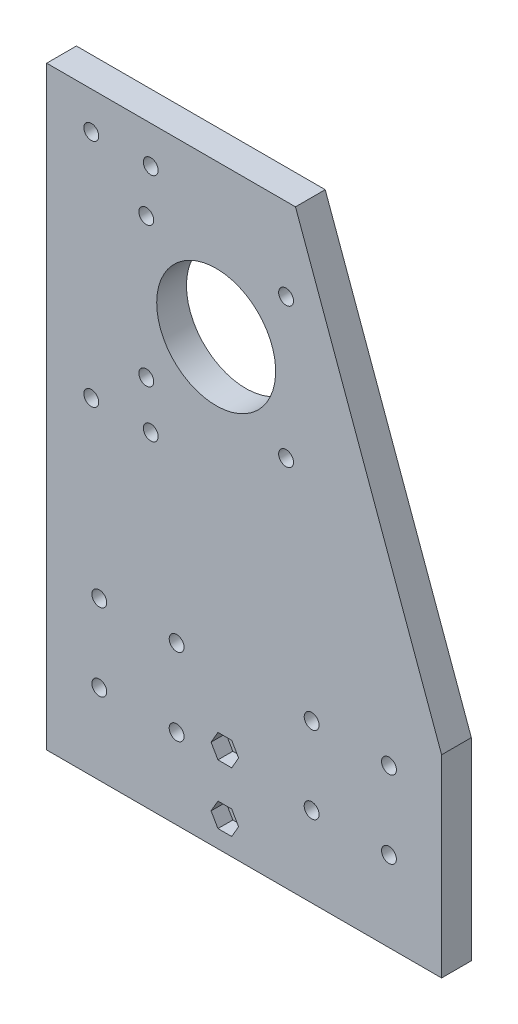
SolidWorks part; units mm, degrees
other "Markup1"
sketch "Sketch3" plane through (0, 200, 35) normal (-0.0073, 0.0178, 0.9998) x (0.9997, -0.0226, 0.0077)
ref_plane "Front Plane" through (0, 0, 0) normal (0, 0, 1) x (1, 0, 0)
ref_plane "Top Plane" through (0, 0, 0) normal (0, 1, 0) x (1, 0, 0)
ref_plane "Right Plane" through (0, 0, 0) normal (1, 0, 0) x (0, 0, -1)
sketch "Sketch1" plane through (0, 0, 0) normal (0, 0, 1) x (1, 0, 0)
  line L0 (66.4, -5.8678) -> (66.4, 56.1407) construction
  line L5 (0, 0) -> (132.8, 0)
  line L6 (0, 0) -> (0, 200)
  line L7 (0, 200) -> (83.664, 200)
  line L8 (132.8, 0) -> (132.8, 65)
  line L9 (71.4, 57.9012) -> (71.4, -9.8319) construction
  line L23 (102.1, 57.9012) -> (102.1, -7.5742) construction
  line L24 (83.9369, 40) -> (119.8285, 40) construction
  line L25 (52.3456, 19.92) -> (67.8875, 19.92) construction
  line L26 (64.535, 29.92) -> (62.2225, 33.9254)
  line L27 (62.2225, 33.9254) -> (57.5975, 33.9254)
  line L28 (57.5975, 33.9254) -> (55.285, 29.92)
  line L29 (55.285, 29.92) -> (57.5975, 25.9146)
  line L30 (57.5975, 25.9146) -> (62.2225, 25.9146)
  line L31 (62.2225, 25.9146) -> (64.535, 29.92)
  line L32 (62.2225, 13.9254) -> (64.535, 9.92)
  line L33 (57.5975, 13.9254) -> (62.2225, 13.9254)
  line L34 (55.285, 9.92) -> (57.5975, 13.9254)
  line L35 (57.5975, 5.9146) -> (55.285, 9.92)
  line L36 (62.2225, 5.9146) -> (57.5975, 5.9146)
  line L37 (64.535, 9.92) -> (62.2225, 5.9146)
  line L38 (132.8, 65) -> (83.664, 200)
  circle A12 centre (115.1, 27) radius 2.5
  circle A13 centre (89.1, 27) radius 2.5
  circle A14 centre (115.1, 53) radius 2.5
  circle A15 centre (89.1, 53) radius 2.5
  circle A16 centre (17.7, 53) radius 2.5
  circle A17 centre (17.7, 27) radius 2.5
  circle A18 centre (43.7, 27) radius 2.5
  circle A19 centre (43.7, 53) radius 2.5
  circle A20 centre (59.91, 29.92) radius 4.0054 construction
  circle A21 centre (59.91, 29.92) radius 2.5
  circle A23 centre (59.91, 9.92) radius 2.5
  dimension "D4" = 5
  dimension "D13" = 5
  dimension "D1" = 200
  dimension "D2" = 132.8
  dimension "D3" = 26
  dimension "D5" = 61.4
  dimension "D6" = 30.7
  dimension "D7" = 27
  dimension "D8" = 13
  dimension "D9" = 29.92
  dimension "D10" = 10
  dimension "D11" = 9.25
  dimension "D12" = 11.49
  dimension "D14" = 65
  dimension "D15" = 20
  dimension "D16" = 9.92
extrude "Boss-Extrude1" add sketch "Sketch1" along normal blind 10 contours L8 L38 L7 L6 L5 A19 A17 A16 A14 A13 A12 L32 L37 L36 L35 L34 L33 L31 L30 L29 L28 L27 L26 A15 A18 | L30 L31 L26 L27 L28 L29 A21 | L37 L32 L33 L34 L35 L36 region at (59.2103, 92.8578, 0) region at (63.2728, 27.9785, 0) region at (63.2728, 11.8615, 0)
extrude "Cut-Extrude1" cut sketch "Sketch1<3>" along normal blind 5 from offset 5 contours L30 L31 L26 L27 L28 L29 A21 | L37 L32 L33 L34 L35 L36 region at (63.2728, 27.9785, 0) region at (63.2728, 11.8615, 0)
sketch "Sketch1<3>" plane through (0, 0, 0) normal (0, 0, 1) x (1, 0, 0) same geometry as "Sketch1"
sketch "Sketch4" plane through (0, 0, 0) normal (0, 0, -1) x (-1, 0, 0)
  line L0 (0, 0) -> (0, 200) construction
  line L1 (0, 200) -> (-83.664, 200) construction
  line L2 (-35, 187.5) -> (-35, 110) construction
  line L4 (-33.5, 125.25) -> (-80.5, 125.25) construction
  line L5 (-33.5, 125.25) -> (-33.5, 172.25) construction
  line L6 (-33.5, 172.25) -> (-80.5, 172.25) construction
  line L7 (-80.5, 125.25) -> (-80.5, 172.25) construction
  line L8 (-33.5, 125.25) -> (-80.5, 172.25) construction
  line L9 (-33.5, 172.25) -> (-80.5, 125.25) construction
  circle A0 centre (-15, 187.5) radius 2.5
  circle A2 centre (-35, 187.5) radius 2.5
  circle A3 centre (-35, 110) radius 2.5
  circle A4 centre (-15, 110) radius 2.5
  circle A5 centre (-57, 148.75) radius 20
  circle A6 centre (-33.5, 172.25) radius 2.5
  circle A13 centre (-33.5, 125.25) radius 2.5
  circle A14 centre (-80.5, 125.25) radius 2.5
  circle A15 centre (-80.5, 172.25) radius 2.5
  point P30 (-57, 145)
  point P31 (-57, 142.5)
  point P32 (-57, 148.75)
  dimension "D1" = 5
  dimension "D9" = 40
  dimension "D12" = 5
  dimension "D2" = 20
  dimension "D3" = 15
  dimension "D4" = 12.5
  dimension "D5" = 2
  dimension "D6" = 77.5
  dimension "D7" = 38.75
  dimension "D8" = 57
  dimension "D10" = 47
  dimension "D11" = 47
  dimension "D13" = 4
extrude "Cut-Extrude2" cut sketch "Sketch4" against normal through all
